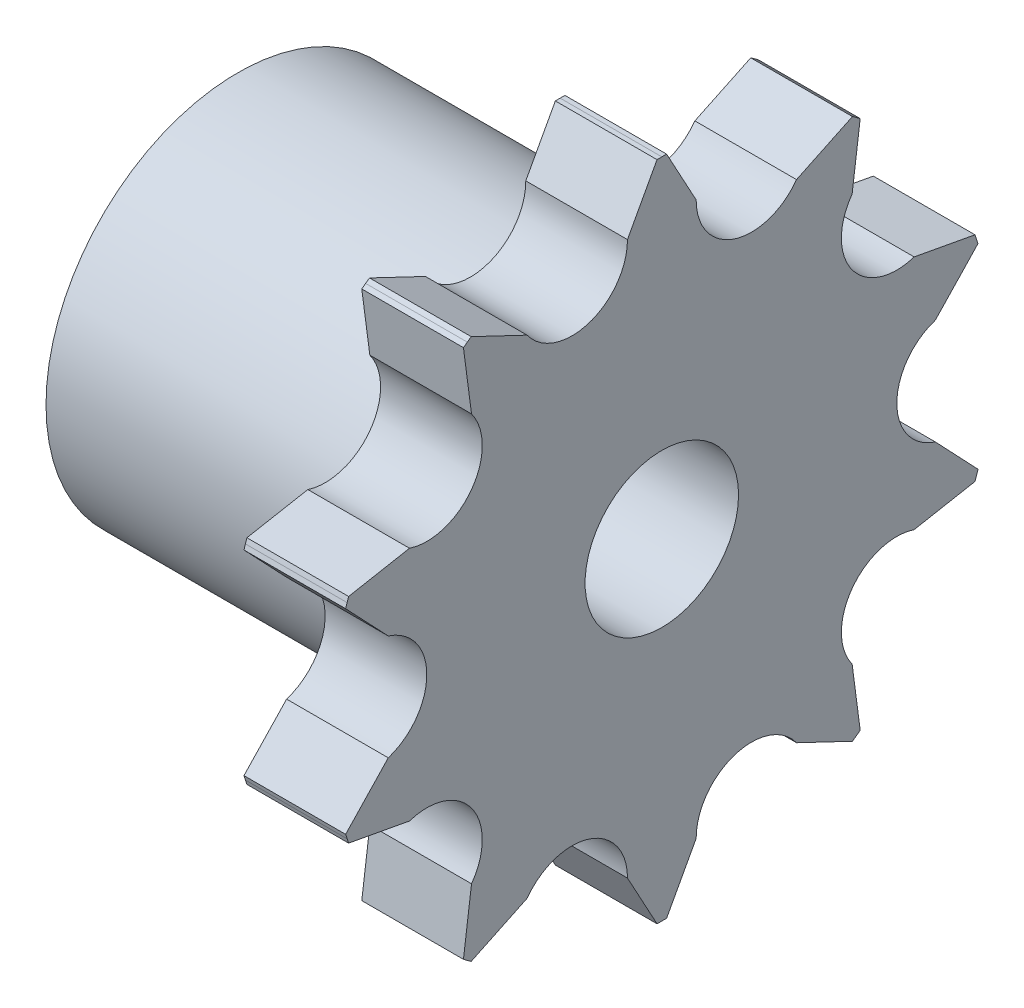
SolidWorks part; units mm, degrees
ref_plane "Front Plane" through (0, 0, 0) normal (0, 0, 1) x (1, 0, 0)
ref_plane "Top Plane" through (0, 0, 0) normal (0, 1, 0) x (1, 0, 0)
ref_plane "Right Plane" through (0, 0, 0) normal (1, 0, 0) x (0, 0, -1)
sketch "Sketch1" plane through (0, 0, 0) normal (1, 0, 0) x (0, 0, -1)
  line L0 (0, 0) -> (0, 17.25)
  line L1 (0, 0) -> (10.1393, 13.9555)
  line L4 (10.1393, 13.9555) -> (9.936, 14.101)
  line L5 (9.936, 14.101) -> (7.0217, 12.7115)
  line L6 (0, 0) -> (3.7855, 11.6504) construction
  line L7 (0.25, 17.2482) -> (1.7909, 14.4111)
  line L8 (10.1393, 13.9555) -> (10.2862, 14.1578)
  line L9 (0, 17.25) -> (0, 17.5)
  circle A0 centre (0, 0) radius 12.25
  circle A1 centre (0, 0) radius 17.25
  circle A2 centre (0, 0) radius 14.5219 construction
  arc A3 (1.7909, 14.4111) -> (7.0217, 12.7115) centre (4.6775, 14.3958) ccw
  circle A4 centre (0, 0) radius 17.5
  point P10 (10.0376, 14.0283)
  point P13 (0.125, 17.2491)
  dimension "D1" = 24.5
  dimension "D2" = 34.5
  dimension "D3" = 0.25
  dimension "D6" = 35
  dimension "D4" = 36
  dimension "D5" = 5.5
extrude "Boss-Extrude1" add sketch "Sketch1" along normal blind 5.3 contours A3 A0 L1 L4 L5 | A3 L7 A1 L0 A0 | L1 A0 L0 region at (0, 7.6398, -2.4823) region at (0, 14.0209, -0.9536) region at (0, 11.9036, -7.4698)
pattern_circular "CirPattern2" count 10 over 360 about axis through (5.3, 0, 0) along (-1, 0, 0) of "Boss-Extrude1" reverse direction yes
sketch "Sketch2" plane through (0, 0, 0) normal (-1, 0, 0) x (0, 0, 1)
  circle A0 centre (0, 0) radius 10
  circle A1 centre (0, 0) radius 4
  dimension "D1" = 8
  dimension "D2" = 20
extrude "Boss-Extrude2" add sketch "Sketch2" along normal blind 16.8
extrude "Cut-Extrude1" cut sketch "Sketch2<2>" against normal blind 16.8 contours A1 region at (0, 0, 0)
sketch "Sketch2<2>" plane through (0, 0, 0) normal (-1, 0, 0) x (0, 0, 1) same geometry as "Sketch2"
